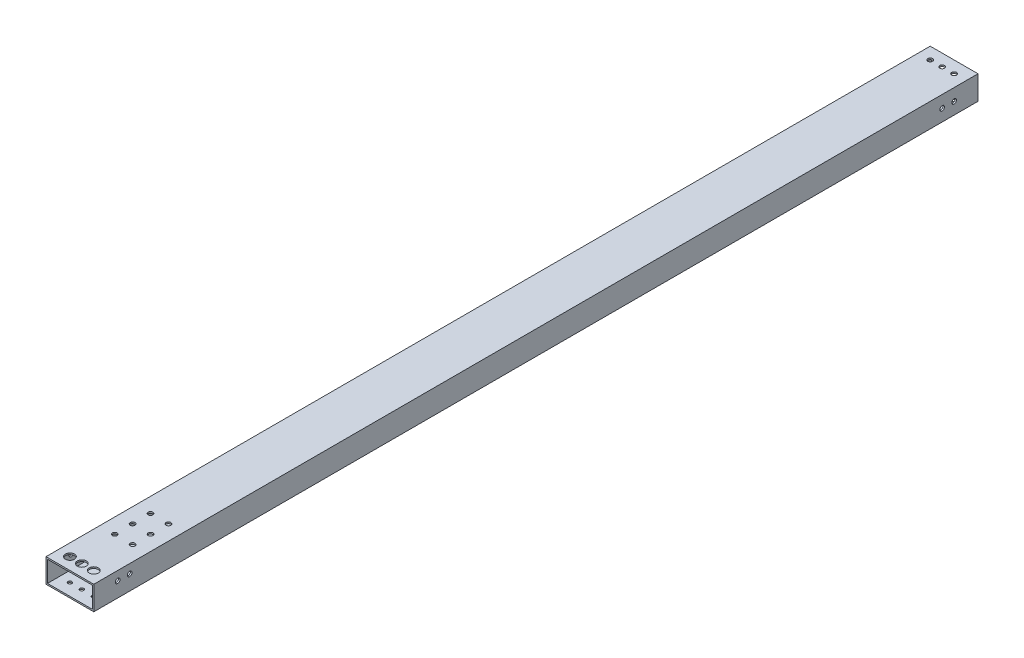
SolidWorks part; units mm, degrees
material "6061-T6 (SS)"
ref_plane "Front Plane" through (0, 0, 0) normal (0, 0, 1) x (1, 0, 0)
ref_plane "Top Plane" through (0, 0, 0) normal (0, 1, 0) x (1, 0, 0)
ref_plane "Right Plane" through (0, 0, 0) normal (1, 0, 0) x (0, 0, -1)
sketch "Sketch1" plane through (0, 0, 0) normal (0, 0, 1) x (1, 0, 0)
  line L0 (-23.8125, 11.1125) -> (23.8125, 11.1125)
  line L1 (-25.4, -12.7) -> (25.4, -12.7)
  line L2 (-25.4, -12.7) -> (-25.4, 12.7)
  line L3 (-25.4, 12.7) -> (25.4, 12.7)
  line L4 (25.4, -12.7) -> (25.4, 12.7)
  line L5 (-25.4, -12.7) -> (25.4, 12.7) construction
  line L6 (-25.4, 12.7) -> (25.4, -12.7) construction
  line L7 (23.8125, -11.1125) -> (23.8125, 11.1125)
  line L8 (-23.8125, -11.1125) -> (23.8125, -11.1125)
  line L9 (-23.8125, -11.1125) -> (-23.8125, 11.1125)
  point P0 (0, 0)
  dimension "D1" = 50.8
  dimension "D2" = 25.4
  dimension "D3" = 1.5875
extrude "Boss-Extrude1" add sketch "Sketch1" along normal mid plane 939.8
sketch "Sketch4" plane through (0, 12.7, 0) normal (0, 1, 0) x (1, 0, 0)
  line L0 (25.4, -469.9) -> (-25.4, -469.9) construction
  circle A0 centre (-12.7, -457.2) radius 4.826
  circle A1 centre (0, -457.2) radius 4.826
  circle A2 centre (12.7, -457.2) radius 4.826
  dimension "D1" = 9.652
  dimension "D2" = 12.7
  dimension "D3" = 12.7
  dimension "D4" = 12.7
extrude "Cut-Extrude3" cut sketch "Sketch4" against normal up to surface (1.5875 mm away) contours A0 | A1 | A2 region at (-12.7, 12.7, 457.2) region at (0, 12.7, 457.2) region at (12.7, 12.7, 457.2) up to face at (0, 11.1125, 0)
sketch "Sketch5" plane through (0, -12.7, 0) normal (0, -1, 0) x (1, 0, 0)
  circle A0 centre (-12.7, 457.2) radius 4.826 construction
  circle A1 centre (0, 457.2) radius 4.826 construction
  circle A2 centre (12.7, 457.2) radius 4.826 construction
  circle A3 centre (-12.7, 457.2) radius 4.826
  circle A4 centre (0, 457.2) radius 4.826
  circle A5 centre (12.7, 457.2) radius 4.826
  circle A6 centre (-12.7, 457.2) radius 2.0193
  circle A7 centre (0, 457.2) radius 2.0193
  circle A8 centre (12.7, 457.2) radius 2.0193
  dimension "D1" = 4.0386
  dimension "D2" = 4.0386
  dimension "D3" = 4.0386
extrude "Cut-Extrude4" cut sketch "Sketch5" against normal up to surface (1.5875 mm away) contours A8 | A7 | A6 region at (-12.7, -12.7, 457.2) region at (0, -12.7, 457.2) region at (12.7, -12.7, 457.2) up to face at (0, -11.1125, 0)
sketch "Sketch6" plane through (0, -12.7, 0) normal (0, -1, 0) x (1, 0, 0)
  line L0 (-25.4, -469.9) -> (25.4, -469.9) construction
  circle A0 centre (-12.7, -457.2) radius 2.5527
  circle A1 centre (0, -457.2) radius 2.5527
  circle A2 centre (12.7, -457.2) radius 2.5527
  dimension "D1" = 5.1054
  dimension "D2" = 12.7
  dimension "D3" = 12.7
  dimension "D4" = 12.7
extrude "Cut-Extrude5" cut sketch "Sketch6" against normal through all contours A2 | A1 | A0 region at (-12.7, -12.7, -457.2) region at (0, -12.7, -457.2) region at (12.7, -12.7, -457.2)
sketch "Sketch7" plane through (25.4, 0, 0) normal (1, 0, 0) x (0, 0, -1)
  line L0 (-469.9, -12.7) -> (-469.9, 12.7) construction
  line L2 (469.9, -12.7) -> (469.9, 12.7) construction
  line L3 (-469.9, -12.7) -> (469.9, -12.7) construction
  circle A0 centre (-457.2, 3.175) radius 2.4892
  circle A1 centre (-444.5, 3.175) radius 2.4892
  circle A2 centre (-431.8, 3.175) radius 2.4892
  circle A3 centre (-419.1, 3.175) radius 2.4892
  circle A4 centre (457.2, 0) radius 2.4892
  circle A5 centre (444.5, 0) radius 2.4892
  circle A6 centre (431.8, 0) radius 2.4892
  dimension "D1" = 4.9784
  dimension "D7" = 4.9784
  dimension "D8" = 12.7
  dimension "D2" = 12.7
  dimension "D3" = 12.7
  dimension "D4" = 12.7
  dimension "D5" = 12.7
  dimension "D6" = 15.875
  dimension "D9" = 12.7
  dimension "D10" = 12.7
  dimension "D11" = 12.7
extrude "Cut-Extrude6" cut sketch "Sketch7" against normal through all contours A6 | A5 | A1 | A2 region at (25.4, 3.175, 444.5) region at (25.4, 3.175, 431.8) region at (25.4, 0, -444.5) region at (25.4, 0, -431.8)
sketch "Sketch9" plane through (0, 12.7, 0) normal (0, 1, 0) x (1, 0, 0)
  line L0 (25.4, -469.9) -> (-25.4, -469.9) construction
  circle A0 centre (-12.7, -419.1) radius 2.5527
  circle A1 centre (0, -419.1) radius 2.5527
  circle A2 centre (12.7, -419.1) radius 2.5527
  dimension "D1" = 5.1054
  dimension "D2" = 12.7
  dimension "D3" = 12.7
  dimension "D4" = 50.8
extrude "Cut-Extrude7" [suppressed] cut sketch "Sketch9" against normal through all
sketch "Sketch10" plane through (0, 12.7, 0) normal (0, 1, 0) x (1, 0, 0)
  line L0 (0, -469.9) -> (0, 469.9) construction
  line L1 (25.4, -469.9) -> (-25.4, -469.9) construction
  line L2 (25.4, 469.9) -> (-25.4, 469.9) construction
  circle A0 centre (-9.525, -412.75) radius 2.5527
  circle A1 centre (-9.525, -393.7) radius 2.5527
  circle A2 centre (-9.525, -374.65) radius 2.5527
  circle A3 centre (9.525, -374.65) radius 2.5527
  circle A4 centre (9.525, -393.7) radius 2.5527
  circle A5 centre (9.525, -412.75) radius 2.5527
  dimension "D1" = 5.1054
  dimension "D2" = 9.525
  dimension "D3" = 9.525
  dimension "D4" = 57.15
  dimension "D5" = 19.05
  dimension "D6" = 19.05
extrude "Cut-Extrude8" cut sketch "Sketch10" against normal through all
